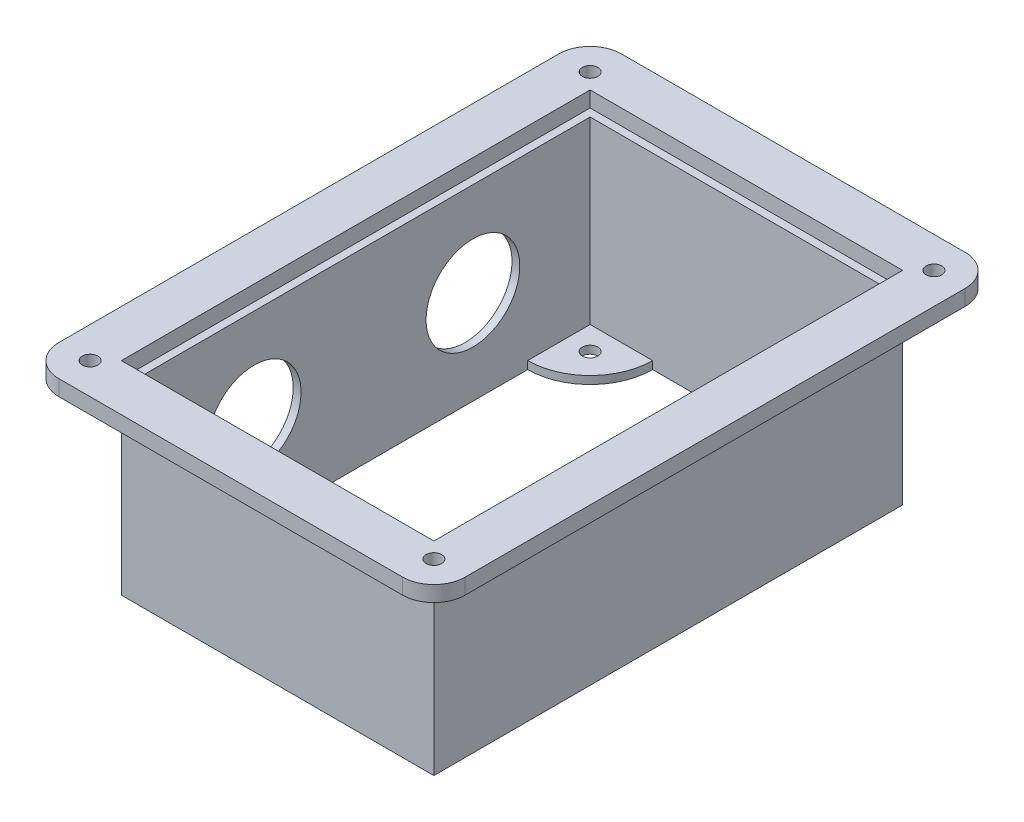
SolidWorks part; units mm, degrees
ref_plane "Alzado" through (0, 0, 0) normal (0, 0, 1) x (1, 0, 0)
ref_plane "Planta" through (0, 0, 0) normal (0, 1, 0) x (1, 0, 0)
ref_plane "Vista lateral" through (0, 0, 0) normal (1, 0, 0) x (0, 0, -1)
sketch "Side-view-large-rect" plane through (0, 0, 0) normal (1, 0, 0) x (0, 0, -1)
  line L1 (0, 0) -> (-120, 0)
  line L2 (0, 0) -> (0, 48)
  line L3 (0, 48) -> (-120, 48)
  line L4 (-120, 0) -> (-120, 48)
  dimension "D1" = 48
  dimension "D2" = 120
extrude "Saliente-Extruir1" add sketch "Side-view-large-rect" along normal blind 80
ref_plane "Plano1" through (40, 0, 0) normal (-1, 0, 0) x (0, 0, 1)
sketch "Croquis4" plane through (40, 0, 0) normal (-1, 0, 0) x (0, 0, 1)
  line L0 (0, 48) -> (-50000, 48) construction
  line L1 (120, 48) -> (120, 0) construction
  line L2 (-12, 48) -> (132, 48)
  line L3 (-12, 48) -> (-12, 52)
  line L4 (-12, 52) -> (132, 52)
  line L5 (132, 48) -> (132, 52)
  line L6 (0, 0) -> (0, 48) construction
  dimension "D1" = 4
  dimension "D2" = 12
  dimension "D3" = 12
extrude "Saliente-Extruir2" add sketch "Croquis4" against normal blind 52 and the other way blind 52
ref_plane "Plano2" through (0, 52, 0) normal (0, 1, 0) x (1, 0, 0)
sketch "Croquis6" plane through (0, 52, 0) normal (0, 1, 0) x (1, 0, 0)
  line L1 (0, 0) -> (80, 0)
  line L2 (0, 0) -> (0, -120)
  line L3 (0, -120) -> (80, -120)
  line L4 (80, 0) -> (80, -120)
  dimension "D1" = 80
  dimension "D2" = 120
  dimension "D3" = 12
  dimension "D4" = 12
extrude "Cortar-Extruir2" cut sketch "Croquis6" against normal blind 4
ref_plane "Plano3" through (0, 48, 0) normal (0, 1, 0) x (1, 0, 0)
sketch "Croquis7" plane through (0, 48, 0) normal (0, 1, 0) x (1, 0, 0)
  line L1 (2, -2) -> (78, -2)
  line L2 (2, -2) -> (2, -118)
  line L3 (2, -118) -> (78, -118)
  line L4 (78, -2) -> (78, -118)
  dimension "D1" = 76
  dimension "D2" = 116
  dimension "D3" = 2
  dimension "D4" = 2
extrude "Cortar-Extruir3" cut sketch "Croquis7" against normal through all
ref_plane "Plano4" through (0, 0, 0) normal (0, -1, 0) x (-1, 0, 0)
sketch "Croquis8" plane through (0, 0, 0) normal (0, -1, 0) x (-1, 0, 0)
  line L1 (-78, -2) -> (-62, -2)
  line L2 (-78, -2) -> (-78, -18)
  line L3 (-78, -18) -> (-62, -18)
  line L4 (-62, -2) -> (-62, -18)
  dimension "D1" = 16
  dimension "D2" = 16
extrude "Saliente-Extruir3" add sketch "Croquis8" against normal blind 2
pattern_linear "MatrizL1" count 2 spacing 60 along (-1, 0, 0) count 2 spacing 100 along (0, 0, 1) of "Saliente-Extruir3"
fillet "Redondeo1" radius 16 1 edges at (62, 1, 18)
fillet "Redondeo2" radius 16 1 edges at (18, 1, 18)
fillet "Redondeo3" radius 16 1 edges at (18, 1, 102)
fillet "Redondeo4" radius 16 1 edges at (62, 1, 102)
fillet "Redondeo5" radius 8 4 edges at (-12, 50, 132) (-12, 50, -12) (92, 50, -12) (92, 50, 132)
sketch "Croquis10" plane through (0, 52, 0) normal (0, 1, 0) x (1, 0, 0)
  line L0 (80, 0) -> (0, 0) construction
  line L1 (0, 0) -> (0, -120) construction
  circle A0 centre (-4, 4) radius 2
  dimension "D1" = 4
  dimension "D2" = 4
  dimension "D3" = 4
extrude "Cortar-Extruir4" cut sketch "Croquis10" against normal through all
pattern_linear "MatrizL2" count 2 spacing 88 along (1, 0, 0) count 2 spacing 128 along (0, 0, 1) of "Cortar-Extruir4"
sketch "Croquis11" plane through (0, 0, 0) normal (0, -1, 0) x (-1, 0, 0)
  line L1 (-62, -2) -> (-18, -2) construction
  circle A0 centre (-72, -8) radius 2
  dimension "D1" = 4
  dimension "D2" = 8
  dimension "D3" = 6
extrude "Cortar-Extruir5" cut sketch "Croquis11" against normal through all
pattern_linear "MatrizL4" count 2 spacing 64 along (-1, 0, 0) count 2 spacing 104 along (0, 0, 1) of "Cortar-Extruir5"
ref_plane "Plano5" through (0, 0, 0) normal (-1, 0, 0) x (0, 0, 1)
sketch "Croquis12" plane through (0, 0, 0) normal (-1, 0, 0) x (0, 0, 1)
  line L1 (120, 0) -> (0, 0) construction
  circle A0 centre (32, 24) radius 12
  circle A1 centre (88, 24) radius 12
  point P7 (0, 0)
  dimension "D1" = 24
  dimension "D2" = 24
  dimension "D3" = 32
  dimension "D4" = 24
  dimension "D5" = 32
extrude "Cortar-Extruir6" cut sketch "Croquis12" against normal up to next (2 mm away)
